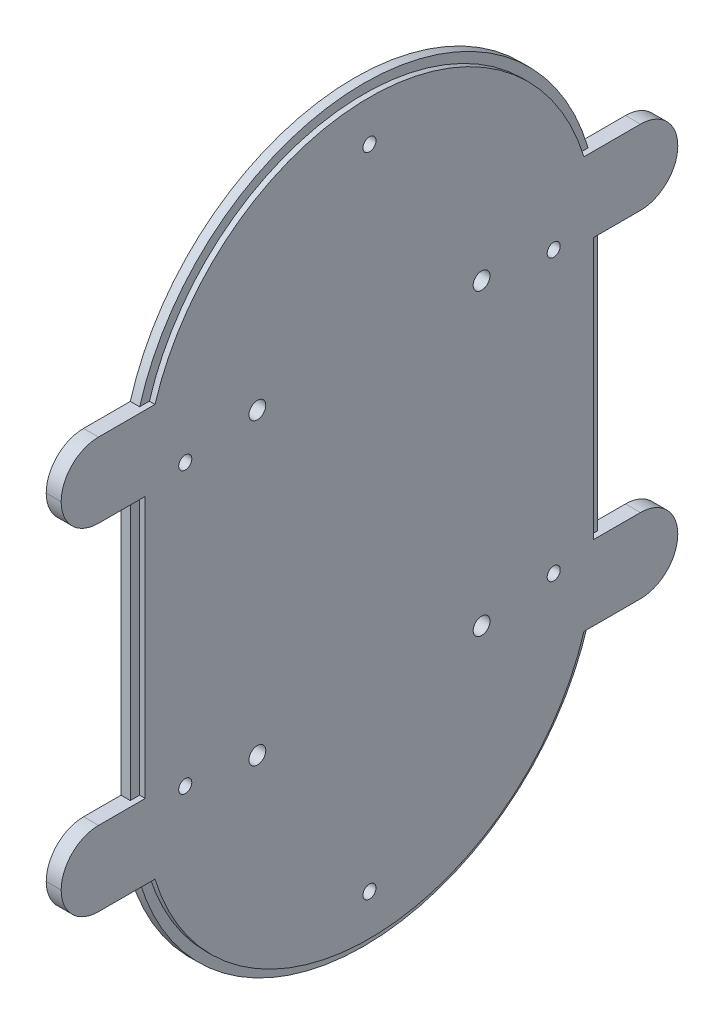
SolidWorks part; units mm, degrees
other "Markup1"
sketch "Sketch8" plane through (4, 100, -82.5) normal (0.9895, 0.0002, -0.1449) x (-0.1441, -0.0996, -0.9845)
ref_plane "Front Plane" through (0, 0, 0) normal (0, 0, 1) x (1, 0, 0)
ref_plane "Top Plane" through (0, 0, 0) normal (0, 1, 0) x (1, 0, 0)
ref_plane "Right Plane" through (0, 0, 0) normal (1, 0, 0) x (0, 0, -1)
sketch "Sketch1" plane through (0, 0, 0) normal (1, 0, 0) x (0, 0, -1)
  line L0 (0, 100) -> (0, 37.5) construction
  line L2 (-62.5, -37.5) -> (-62.5, 37.5)
  line L4 (62.5, -37.5) -> (62.5, 37.5)
  line L7 (0, 0) -> (62.5, 0) construction
  line L8 (0, 0) -> (0, -100) construction
  arc A0 (62.5, 37.5) -> (-62.5, 37.5) centre (0, 37.5) ccw
  arc A1 (62.5, -37.5) -> (-62.5, -37.5) centre (0, -37.5) cw
  point P0 (0, 0)
  dimension "D1" = 75
  dimension "D2" = 62.5
  dimension "D3" = 62.5
  dimension "D4" = 125
extrude "Boss-Extrude1" add sketch "Sketch1" along normal blind 2.5
sketch "Sketch2" plane through (2.5, 0, 0) normal (1, 0, 0) x (0, 0, -1)
  line L2 (-62.5, 37.5) -> (-62.5, -37.5)
  line L3 (62.5, -37.5) -> (62.5, 37.5)
  line L4 (-62.5, 37.5) -> (-62.5, -37.5) construction
  line L5 (62.5, -37.5) -> (62.5, 37.5) construction
  line L8 (-60, 37.5) -> (-60, -37.5)
  line L9 (60, -37.5) -> (60, 37.5)
  line L10 (-60, 37.5) -> (-60, -37.5)
  line L11 (60, -37.5) -> (60, 37.5)
  arc A2 (62.5, 37.5) -> (-62.5, 37.5) centre (0, 37.5) ccw
  arc A3 (-62.5, -37.5) -> (62.5, -37.5) centre (0, -37.5) ccw
  arc A4 (62.5, 37.5) -> (-62.5, 37.5) centre (0, 37.5) ccw construction
  arc A5 (-62.5, -37.5) -> (62.5, -37.5) centre (0, -37.5) ccw construction
  arc A8 (60, 37.5) -> (-60, 37.5) centre (0, 37.5) ccw
  arc A9 (-60, -37.5) -> (60, -37.5) centre (0, -37.5) ccw
  arc A10 (60, 37.5) -> (-60, 37.5) centre (0, 37.5) ccw
  arc A11 (-60, -37.5) -> (60, -37.5) centre (0, -37.5) ccw
  dimension "D1" = 0
  dimension "D2" = 2.5
extrude "Boss-Extrude2" add sketch "Sketch2" along normal blind 1.5
ref_plane "Plane1" through (0, 0, -82.5) normal (0, 0, -1) x (-1, 0, 0)
sketch "Sketch4" plane through (0, 0, -82.5) normal (0, 0, -1) x (-1, 0, 0)
  line L0 (0, 0) -> (0, 100) construction
  line L1 (0, 37.5) -> (0, 100) construction
  line L2 (0, 0) -> (-4, 0) construction
  line L3 (-4, -37.5) -> (-4, 37.5) construction
  line L4 (-4, 97.5) -> (-4, 37.5) construction
  line L5 (0, 35) -> (-4, 35)
  line L6 (0, 35) -> (0, 55)
  line L7 (0, 55) -> (-4, 55)
  line L8 (-4, 35) -> (-4, 55)
  line L9 (0, -55) -> (-4, -55)
  line L10 (-4, -35) -> (-4, -55)
  line L11 (0, -35) -> (-4, -35)
  line L12 (0, -35) -> (0, -55)
  dimension "D1" = 100
  dimension "D2" = 20
  dimension "D3" = 35
extrude "Boss-Extrude3" add sketch "Sketch4" against normal up to next
ref_plane "Plane2" through (0, 0, 0) normal (0, 0, -1) x (-1, 0, 0)
fillet "Fillet1" radius 10 4 edges at (2, -55, -82.5) (2, -35, -82.5) (2, 35, -82.5) (2, 55, -82.5)
sketch "Sketch5" plane through (4, 0, 0) normal (1, 0, 0) x (0, 0, -1)
  circle A0 centre (72.5, 45) radius 2.5
  circle A1 centre (72.5, -45) radius 2.5
  dimension "D1" = 5
  dimension "D2" = 5
mirror "Mirror2" about plane through (0, 0, 0) normal (0, 0, -1) of "Fillet1", "Boss-Extrude3"
sketch "Sketch6" plane through (4, 0, 0) normal (1, 0, 0) x (0, 0, -1)
  line L0 (-35, 0) -> (-60, 0) construction
  line L1 (-35, -45) -> (35, -45) construction
  line L2 (-35, -45) -> (-35, 45) construction
  line L3 (-35, 45) -> (35, 45) construction
  line L4 (35, -45) -> (35, 45) construction
  line L5 (-35, -45) -> (35, 45) construction
  line L6 (-35, 45) -> (35, -45) construction
  line L7 (-60, 35) -> (-60, -35) construction
  line L8 (0, 0) -> (0, 45) construction
  line L9 (0, 0) -> (35, 0) construction
  circle A0 centre (-30, 40) radius 1.5 construction
  circle A2 centre (-30, 40) radius 2.25
  circle A3 centre (30, 40) radius 2.25
  circle A4 centre (30, -40) radius 2.25
  circle A5 centre (-30, -40) radius 2.25
  point P0 (0, 0)
  dimension "D4" = 3
  dimension "D5" = 5
  dimension "D6" = 5
  dimension "D7" = 4.5
  dimension "D1" = 70
  dimension "D2" = 90
  dimension "D3" = 25
extrude "Cut-Extrude2" cut sketch "Sketch6" against normal through all
sketch "Sketch7" plane through (4, 0, 0) normal (1, 0, 0) x (0, 0, -1)
  line L0 (0, 100) -> (0, -100) construction
  line L1 (0, 86.58) -> (0, 37.5) construction
  line L2 (0, 37.5) -> (49.3, 37.5) construction
  line L3 (0, 0) -> (62.5, 0) construction
  line L4 (62.5, -35) -> (62.5, 35) construction
  arc A0 (60, 55) -> (-60, 55) centre (0, 37.5) ccw construction
  arc A1 (-60, -55) -> (60, -55) centre (0, -37.5) ccw construction
  circle A2 centre (0, 86.58) radius 1.75
  circle A3 centre (49.3, 37.5) radius 1.75
  circle A4 centre (-49.3, 37.5) radius 1.75
  circle A5 centre (49.3, -37.5) radius 1.75
  circle A6 centre (0, -86.58) radius 1.75
  circle A7 centre (-49.3, -37.5) radius 1.75
  dimension "D1" = 3.5
  dimension "D5" = 3.5
  dimension "D2" = 13.42
  dimension "D3" = 49.08
  dimension "D4" = 49.3
extrude "Cut-Extrude3" cut sketch "Sketch7" against normal through all
